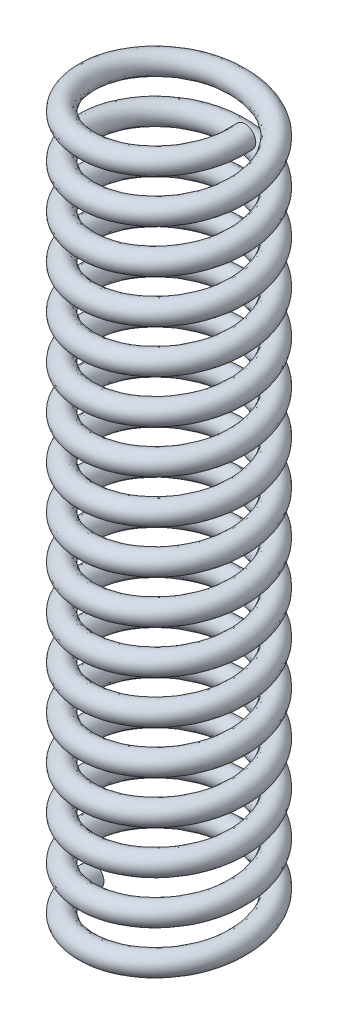
SolidWorks part; units mm, degrees
note: '?' marks a value the reader was unsure of.
material "AISI 304"
ref_plane "Front Plane" through (0, 0, 0) normal (0, 0, 1) x (1, 0, 0)
ref_plane "Top Plane" through (0, 0, 0) normal (0, 1, 0) x (1, 0, 0)
ref_plane "Right Plane" through (0, 0, 0) normal (1, 0, 0) x (0, 0, -1)
ref_axis "SpringAxis" through (0, 1.15, 0) along (0, -1, 0)?
sketch "SpringBodyDiameterS" plane through (0, 0, 0) normal (0, 0, 1) x (1, 0, 0)
  line L0 (0, 0) -> (1.5, 0) construction
  line L1 (0, 0) -> (0, 1) construction
  line L2 (1.75, 0) -> (2, 0) construction
  circle A0 centre (1.75, 0) radius 0.25
  dimension "WireDia" = 0.5
  dimension "RefRevolve" = 1
  dimension "RevolveDia" = 3.5
  dimension "RefID" = 1.5
  dimension "RefOD" = 2
sketch "SpringHelixS" plane through (0, 0, 0) normal (0, 1, 0) x (1, 0, 0)
  circle A0 centre (0, 0) radius 1.75
  dimension "RefDia" = 3.5
curve "SPRING HELIX" pitch 1 height 16.5 turns 16.5 parameters "Height"=16.5, "Pitch"=1
sweep "SPRING" add profiles "SpringBodyDiameterS" path "SPRING HELIX"
